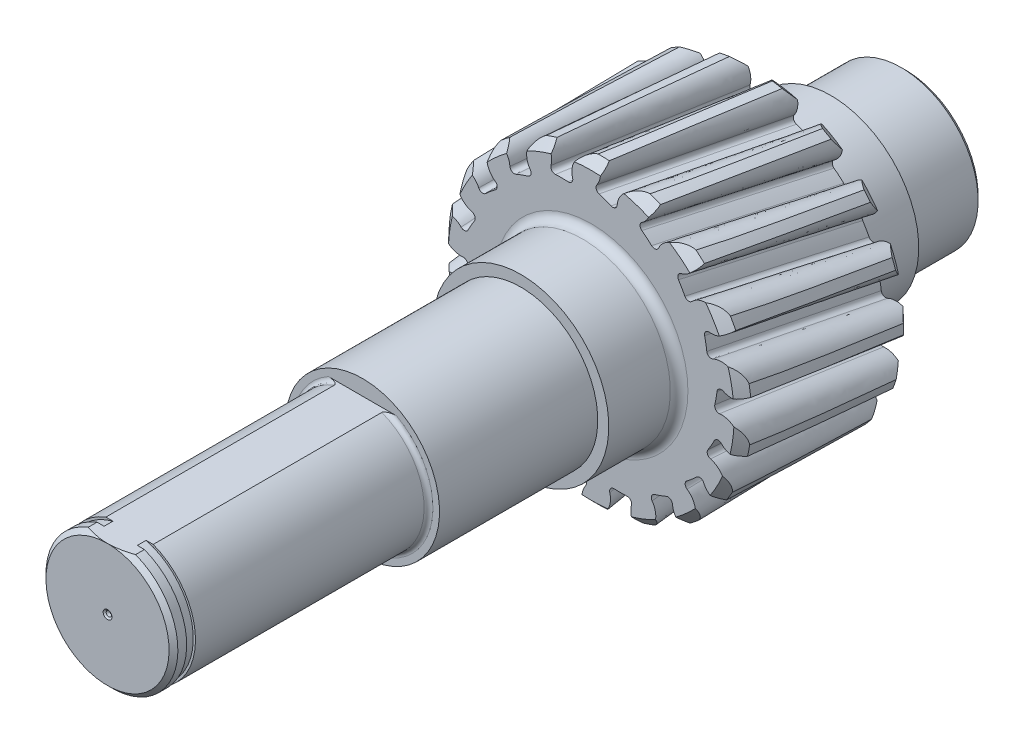
SolidWorks part; units mm, degrees
ref_plane "Front Plane" through (0, 0, 0) normal (0, 0, 1) x (1, 0, 0)
ref_plane "Top Plane" through (0, 0, 0) normal (0, 1, 0) x (1, 0, 0)
ref_plane "Right Plane" through (0, 0, 0) normal (1, 0, 0) x (0, 0, -1)
sketch "Sketch1" plane through (0, 0, 0) normal (0, 0, 1) x (1, 0, 0)
  line L1 (-34.1006, 32.4483) -> (-23.3303, 32.4483)
  arc A0 (-34.1006, 32.4483) -> (-23.3303, 32.4483) centre (-28.7154, 18.4483) ccw
  dimension "D1" = 30
  dimension "D2" = 14
extrude "Section No.1" add sketch "Sketch1" along normal blind 58
sketch "Sketch2" plane through (0, 0, 0) normal (0, 0, -1) x (-1, 0, 0)
  circle A0 centre (28.7154, 18.4483) radius 17.5
  dimension "D1" = 35
extrude "Section No.2" add sketch "Sketch2" along normal blind 36
sketch "Sketch3" plane through (0, 0, -36) normal (0, 0, -1) x (-1, 0, 0)
  circle A0 centre (28.7154, 18.4483) radius 20
  dimension "D1" = 40
extrude "Section No.3" add sketch "Sketch3" along normal blind 16
sketch "Sketch4" plane through (0, 0, -52) normal (0, 0, -1) x (-1, 0, 0)
  circle A0 centre (28.7154, 18.4483) radius 34.5
  dimension "D1" = 69
extrude "Section No.4" add sketch "Sketch4" along normal blind 38.5
sketch "Sketch5" plane through (0, 0, -90.5) normal (0, 0, -1) x (-1, 0, 0)
  circle A0 centre (28.7154, 18.4483) radius 20
  dimension "D1" = 40
extrude "Section No.5" add sketch "Sketch5" along normal blind 16
sketch "Sketch6" plane through (0, 0, -106.5) normal (0, 0, -1) x (-1, 0, 0)
  circle A0 centre (28.7154, 18.4483) radius 17.5
  dimension "D1" = 35
extrude "Section No.6" add sketch "Sketch6" along normal blind 17
chamfer "Section No.1 chamfer" distance 1 1 edges at (-28.7154, 3.4483, 58)
chamfer "Section No.6 chamfer" distance 1 angle 45 1 edges at (-46.2154, 18.4483, -123.5)
fillet "Section No.1-2 fillet" radius 1 1 edges at (-28.7154, 3.4483, 0)
fillet "Section No.3-4,4-5 fillet" radius 2 2 edges at (-48.7154, 18.4483, -90.5) (-48.7154, 18.4483, -52)
hole_wizard "Mounting hole No.1" positions "3DSketch11" profile "Sketch18" hole size "M1" standard "ISO"
sketch3d "3DSketch11"
  line L0 (-28.7154, 18.4483, 57) -> (-28.7154, 18.4483, 58) construction
  point P0 (-28.7154, 18.4483, 58)
sketch "Sketch18" plane through (-28.7154, 18.4483, 58) normal (1, 0, 0) x (0, -1, 0)
  line L0 (0, 0) -> (0, 0.5798)
  line L1 (0, 0.5798) -> (0.6, 0.3)
  line L2 (0.6, 0.3) -> (0.6, 0.4)
  line L3 (0.6, 0.4) -> (1, 0)
  line L5 (1, 0) -> (0, 0)
  line L6 (-0.6, 0.4) -> (-1, 0) construction
  line L10 (0, 0.5798) -> (-0.6, 0.3) construction
  line L11 (0, -6.35) -> (0, 107.95) construction
  dimension "Hole Dia." = 1.2
  dimension "Hole Depth" = 0.3
  dimension "Near C'Sink Dia." = 2
  dimension "Near C'Sink Angle" = 90
  dimension "Drill Angle" = 130
hole_wizard "Mounting hole No.2" positions "3DSketch10" profile "Sketch17" hole size "M1" standard "ISO"
sketch3d "3DSketch10"
  line L0 (-28.7154, 18.4483, -122.5) -> (-28.7154, 18.4483, -123.5) construction
  point P0 (-28.7154, 18.4483, -123.5)
sketch "Sketch17" plane through (-28.7154, 18.4483, -123.5) normal (1, 0, 0) x (0, 1, 0)
  line L0 (0, 0) -> (0, 0.5798)
  line L1 (0, 0.5798) -> (0.6, 0.3)
  line L2 (0.6, 0.3) -> (0.6, 0.4)
  line L3 (0.6, 0.4) -> (1, 0)
  line L5 (1, 0) -> (0, 0)
  line L6 (-0.6, 0.4) -> (-1, 0) construction
  line L10 (0, 0.5798) -> (-0.6, 0.3) construction
  line L11 (0, -6.35) -> (0, 107.95) construction
  dimension "Hole Dia." = 1.2
  dimension "Hole Depth" = 0.3
  dimension "Near C'Sink Dia." = 2
  dimension "Near C'Sink Angle" = 90
  dimension "Drill Angle" = 130
sketch "Sketch19" plane through (0, 0, -90.5) normal (0, 0, -1) x (-1, 0, 0)
  line L0 (28.6191, 18.4494) -> (28.6191, 53.4994) construction
  line L1 (21.8191, 18.4494) -> (21.8191, 53.4994) construction
  line L2 (35.4191, 18.4494) -> (35.4191, 53.4994) construction
  line L3 (30.1191, 18.4494) -> (30.1191, 53.4994) construction
  line L4 (27.1191, 18.4494) -> (27.1191, 53.4994) construction
  arc A0 (34.6725, 52.9727) -> (22.5658, 52.9727) centre (28.6191, 18.4494) ccw
  arc A1 (30.0668, 46.0668) -> (27.1715, 46.0668) centre (28.6191, 18.4494) ccw
  arc A2 (34.6725, 52.9727) -> (31.0828, 47.3326) centre (35.4191, 48.5351) ccw
  arc A3 (22.5658, 52.9727) -> (26.1555, 47.3326) centre (21.8191, 48.5351) cw
  arc A4 (31.0828, 47.3326) -> (30.0668, 46.0668) centre (30.1191, 47.0654) cw
  arc A5 (26.1555, 47.3326) -> (27.1715, 46.0668) centre (27.1191, 47.0654) ccw
  circle A6 centre (28.6191, 18.4494) radius 35.05 construction
  circle A7 centre (28.6191, 18.4494) radius 27.5 construction
  dimension "D1" = 1
  dimension "D2" = 4.5
  dimension "D3" = 4.5
  dimension "D4" = 1.5
  dimension "D5" = 70.1
  dimension "D6" = 55
  dimension "D7" = 6.8
  dimension "D8" = 6.8
  dimension "D9" = 1.5
ref_axis "Tooth axis" through (-28.7154, 18.4483, -90.5) along (0, 0, 1)
chamfer "Tooth chamfer" distance 2 2 edges at (-63.2154, 18.4483, -52) (-63.2154, 18.4483, -90.5)
ref_plane "Plane1" through (0, 0, 55) normal (0, 0, 1) x (1, 0, 0)
sketch "Sketch20" plane through (0, 0, 55) normal (0, 0, 1) x (1, 0, 0)
  circle A0 centre (-28.7154, 18.4483) radius 15
  circle A1 centre (-28.7154, 18.4483) radius 14.5
  dimension "D1" = 30
  dimension "D2" = 29
extrude "Cut-Extrude3" cut sketch "Sketch20" against normal blind 2
ref_plane "Plane2" through (0, 53.4994, 0) normal (0, 1, 0) x (-1, 0, 0)
sketch "Sketch21" plane through (0, 53.4994, 0) normal (0, 1, 0) x (-1, 0, 0)
  line L0 (28.6191, -90.5) -> (35.4077, -52)
  line L1 (61.2154, -52) -> (-3.7846, -52) construction
sweep "Cut-Sweep1" cut profiles "Sketch19" path "Sketch21"
pattern_circular "CirPattern1" count 18 over 360 about axis through (-28.7154, 18.4483, -90.5) along (0, 0, 1) of "Cut-Sweep1"
